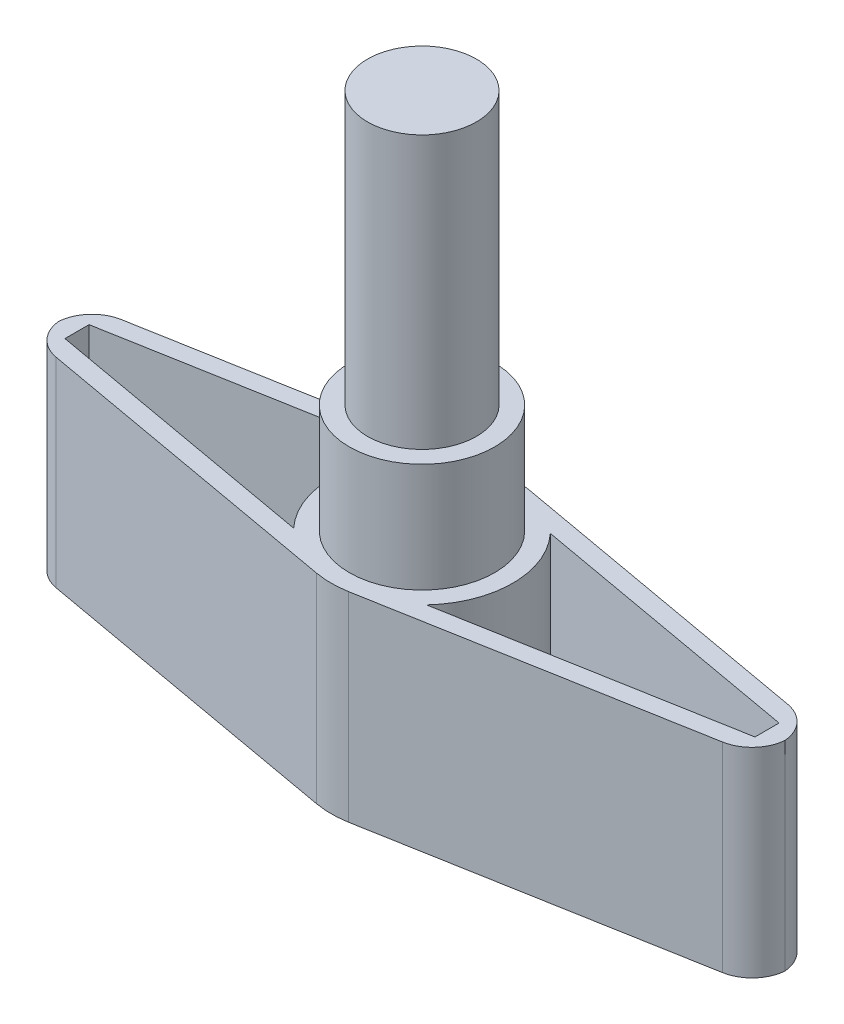
SolidWorks part; units mm, degrees
material "Rubber"
ref_plane "Front Plane" through (0, 0, 0) normal (0, 0, 1) x (1, 0, 0)
ref_plane "Top Plane" through (0, 0, 0) normal (0, 1, 0) x (1, 0, 0)
ref_plane "Right Plane" through (0, 0, 0) normal (1, 0, 0) x (0, 0, -1)
sketch "Sketch1" plane through (0, 0, 0) normal (0, 1, 0) x (1, 0, 0)
  line L1 (-20.0002, 1.5009) -> (-20.0002, -1.5009)
  line L2 (-20.0002, 1.5009) -> (-0.8806, 4.9218)
  line L3 (-20.0002, -1.5009) -> (-0.8806, -4.9218)
  line L4 (-19.0002, -0.6639) -> (-19.0002, 0.6639)
  line L5 (-18.824, -0.6954) -> (-19.0002, -0.6639)
  line L6 (-18.824, 0.6954) -> (-3.6576, 3.4091)
  line L7 (-18.824, 0.6954) -> (-19.0002, 0.6639)
  line L8 (-18.824, -0.6954) -> (-3.6576, -3.4091)
  line L10 (18.824, 0.6954) -> (19.0002, 0.6639)
  line L11 (18.824, 0.6954) -> (3.6576, 3.4091)
  line L12 (18.824, -0.6954) -> (19.0002, -0.6639)
  line L13 (19.0002, -0.6639) -> (19.0002, 0.6639)
  line L14 (20.0002, -1.5009) -> (0.8806, -4.9218)
  line L15 (20.0002, 1.5009) -> (0.8806, 4.9218)
  line L16 (20.0002, 1.5009) -> (20.0002, -1.5009)
  line L18 (18.824, -0.6954) -> (3.6576, -3.4091)
  arc A2 (-3.6576, 3.4091) -> (-3.6576, -3.4091) centre (0, 0) ccw
  arc A3 (0.8806, 4.9218) -> (-0.8806, 4.9218) centre (0, 0) ccw
  arc A4 (3.6576, -3.4091) -> (3.6576, 3.4091) centre (0, 0) ccw
  arc A5 (-0.8806, -4.9218) -> (0.8806, -4.9218) centre (0, 0) ccw
  point P7 (-20.0002, 0)
  point P29 (20.0002, 0)
extrude "Boss-Extrude1" add sketch "Sketch1" along normal blind 10
sketch "Sketch2" plane through (0, 0, 0) normal (0, -1, 0) x (1, 0, 0)
  line L0 (-20.0002, 1.5009) -> (-0.8806, 4.9218)
  line L1 (-20.0002, 1.5009) -> (-20.0002, -1.5009)
  line L2 (20.0002, 1.5009) -> (20.0002, -1.5009)
  line L3 (-20.0002, -1.5009) -> (-0.8806, -4.9218)
  line L4 (0.8806, -4.9218) -> (20.0002, -1.5009)
  line L5 (20.0002, 1.5009) -> (0.8806, 4.9218)
  arc A1 (-0.8806, -4.9218) -> (0.8806, -4.9218) centre (0, 0) ccw
  arc A2 (0.8806, 4.9218) -> (-0.8806, 4.9218) centre (0, 0) ccw
extrude "Boss-Extrude2" add sketch "Sketch2" along normal blind 1
sketch "Sketch3" plane through (0, 10, 0) normal (0, 1, 0) x (1, 0, 0)
  circle A0 centre (0, 0) radius 4
extrude "Boss-Extrude3" add sketch "Sketch3" along normal blind 6
sketch "Sketch4" plane through (0, 16, 0) normal (0, 1, 0) x (1, 0, 0)
  circle A0 centre (0, 0) radius 3
extrude "Boss-Extrude4" add sketch "Sketch4" along normal blind 15
cosmetic thread "Cosmetic Thread1" parameters "D2"=5
fillet "Fillet1" radius 2 4 edges at (20.0002, 4.5, 1.5009) (20.0002, 4.5, -1.5009) (-20.0002, 4.5, -1.5009) (-20.0002, 4.5, 1.5009)
